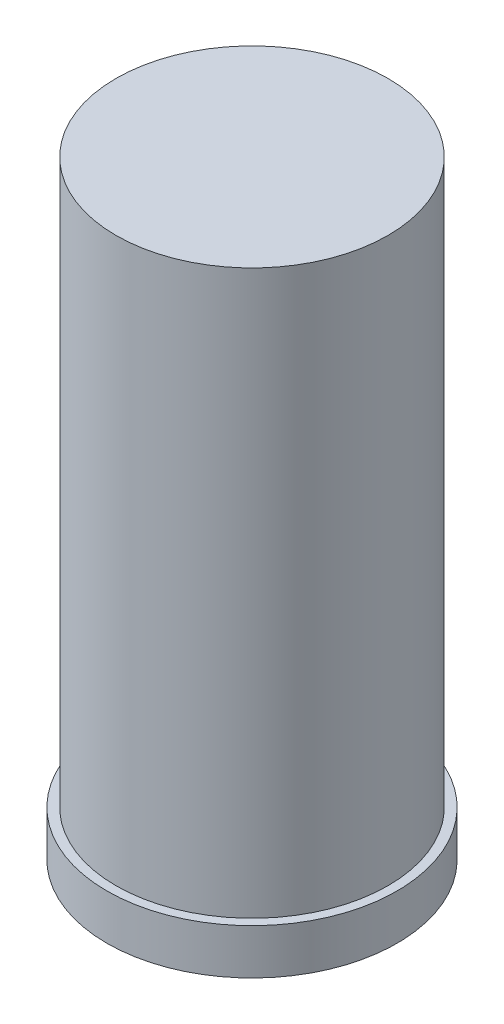
SolidWorks part; units mm, degrees
ref_plane "Front Plane" through (0, 0, 0) normal (0, 0, 1) x (1, 0, 0)
ref_plane "Top Plane" through (0, 0, 0) normal (0, 1, 0) x (1, 0, 0)
ref_plane "Right Plane" through (0, 0, 0) normal (1, 0, 0) x (0, 0, -1)
sketch "Sketch1" plane through (0, 0, 0) normal (0, 1, 0) x (1, 0, 0)
  circle A0 centre (0, 0) radius 15
  circle A1 centre (0, 0) radius 4
  circle A2 centre (0, 0) radius 16
  dimension "D1" = 30
  dimension "D2" = 8
  dimension "D3" = 1
extrude "Boss-Extrude1" add sketch "Sketch1" along normal blind 67.12 contours A1 | A0 A1 region at (-14.5757, 0, 0) region at (0, 0, 0)
extrude "Cut-Extrude1" cut sketch "Sketch1<3>" along normal blind 7 contours A1 region at (0, 0, 0)
sketch "Sketch1<3>" plane through (0, 0, 0) normal (0, 1, 0) x (1, 0, 0) same geometry as "Sketch1"
extrude "Boss-Extrude2" add sketch "Sketch1<4>" along normal blind 5 contours A2 A0 region at (-15.5475, 0, 0)
sketch "Sketch1<4>" plane through (0, 0, 0) normal (0, 1, 0) x (1, 0, 0) same geometry as "Sketch1"
